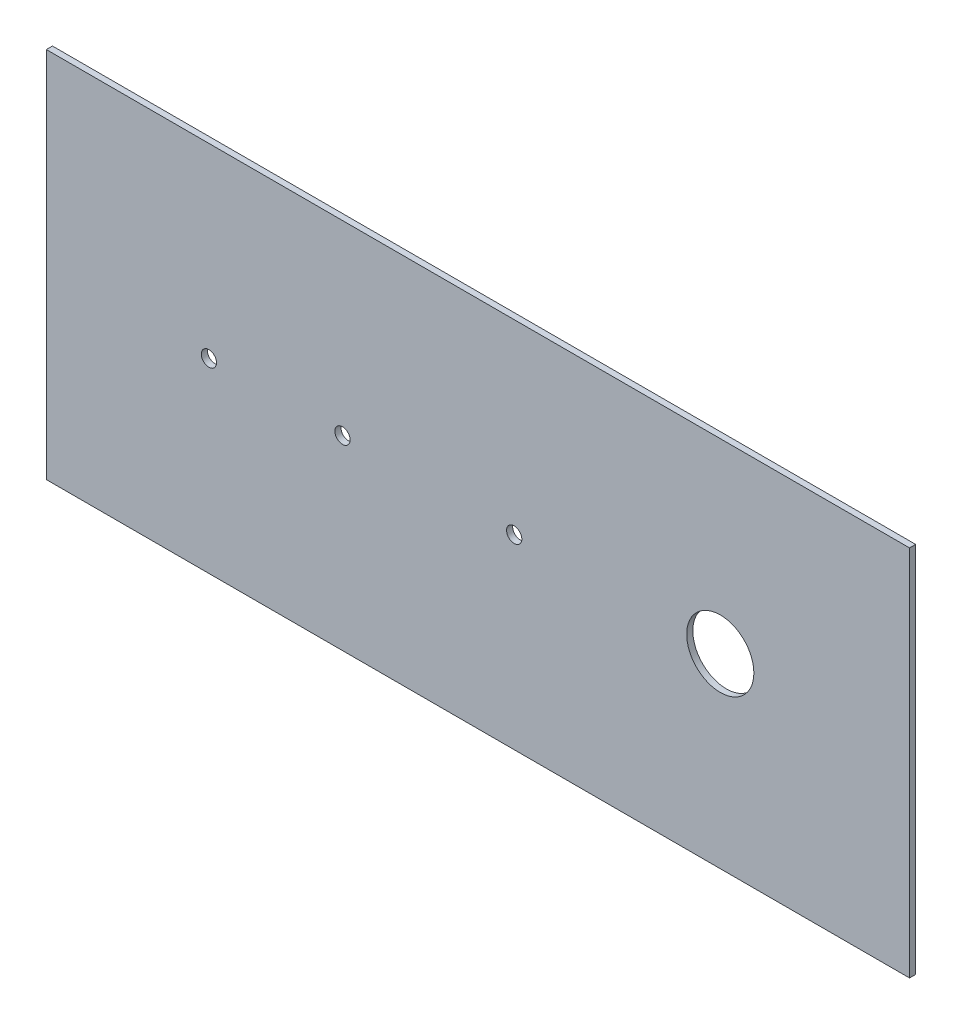
SolidWorks part; units mm, degrees
material "Сталь ШХ15 ГОСТ 801-78"
ref_plane "Plane1" through (0, 0, 0) normal (0, 0, 1) x (1, 0, 0)
ref_plane "Plane2" through (0, 0, 0) normal (0, 1, 0) x (1, 0, 0)
ref_plane "Plane3" through (0, 0, 0) normal (1, 0, 0) x (0, 0, -1)
sketch "Эскиз1" plane through (0, 0, 0) normal (0, 0, 1) x (1, 0, 0)
  line L0 (0, 61) -> (282.75, 61) construction
  line L1 (0, 0) -> (282.75, 0)
  line L2 (0, 0) -> (0, 122)
  line L3 (0, 122) -> (282.75, 122)
  line L4 (282.75, 0) -> (282.75, 122)
  circle A0 centre (22, 61) radius 11
  circle A1 centre (53.25, 61) radius 2.5
  circle A2 centre (97, 61) radius 2.5
  circle A3 centre (153.25, 61) radius 2.5
  circle A4 centre (220.75, 61) radius 11
  dimension "D3" = 22
  dimension "D4" = 22
  dimension "D5" = 5
  dimension "D6" = 31.25
  dimension "D9" = 62
  dimension "D10" = 22
  dimension "D1" = 122
  dimension "D2" = 67.5
  dimension "D7" = 43.75
  dimension "D8" = 56.25
extrude "Бобышка-Вытянуть1" add sketch "Эскиз1" along normal blind 2 contours L2 L0 A0 A1 A2 A3 A4 L4 L3 | L0 L2 L1 L4 A4 A3 A2 A1 A0 | A0 L0 | L0 A0 region at (141.8968, 92.1347, 0) region at (141.8968, 29.8653, 0) region at (22, 65.6685, 0) region at (22, 56.3315, 0)
